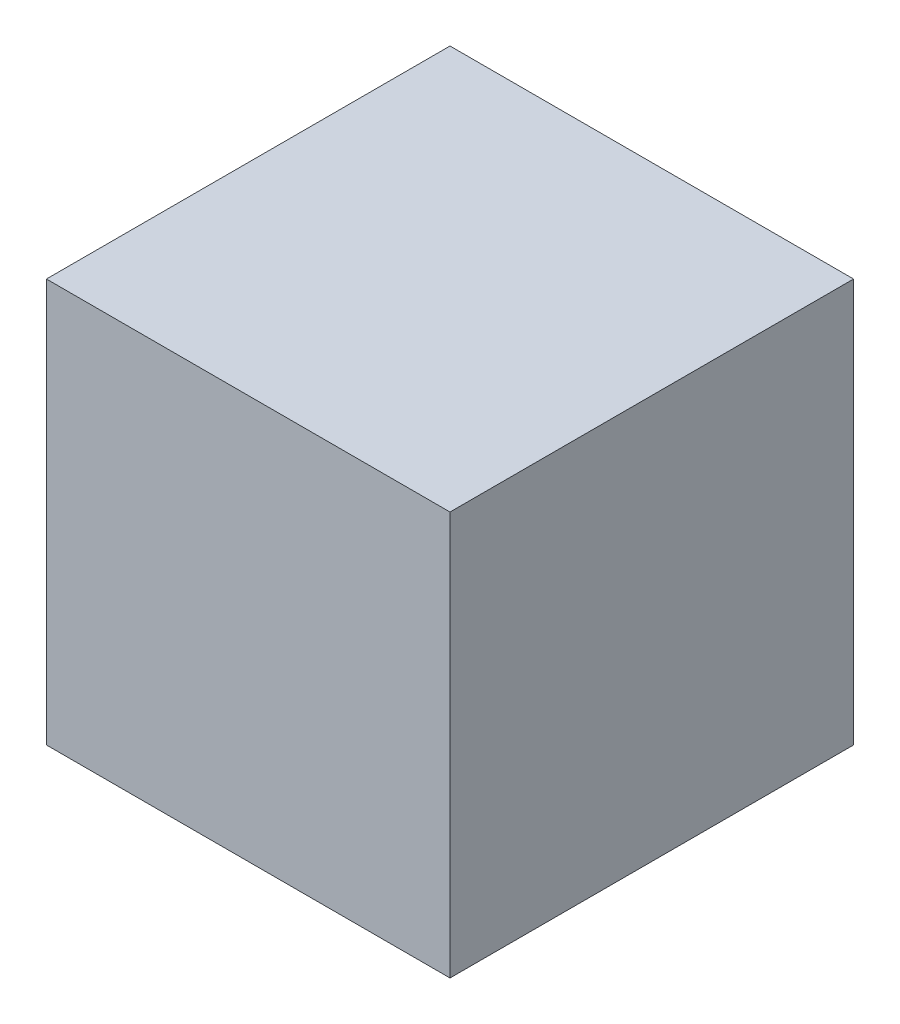
SolidWorks part; units mm, degrees
ref_plane "Front Plane" through (0, 0, 0) normal (0, 0, 1) x (1, 0, 0)
ref_plane "Top Plane" through (0, 0, 0) normal (0, 1, 0) x (1, 0, 0)
ref_plane "Right Plane" through (0, 0, 0) normal (1, 0, 0) x (0, 0, -1)
sketch "Sketch1" plane through (0, 0, 0) normal (0, 1, 0) x (1, 0, 0)
  line L1 (-20, -20) -> (20, -20)
  line L2 (-20, -20) -> (-20, 20)
  line L3 (-20, 20) -> (20, 20)
  line L4 (20, -20) -> (20, 20)
  dimension "D1" = 40
  dimension "D2" = 40
  dimension "D3" = 20
  dimension "D4" = 20
extrude "Boss-Extrude1" add sketch "Sketch1" along normal blind 20 and the other way blind 20
ref_axis "Zaxis" through (0, 22, 0) along (0, -1, 0)
ref_axis "Yaxis" through (22, 0, 0) along (-1, 0, 0)
ref_axis "Xaxis" through (0, 0, 22) along (0, 0, -1)
